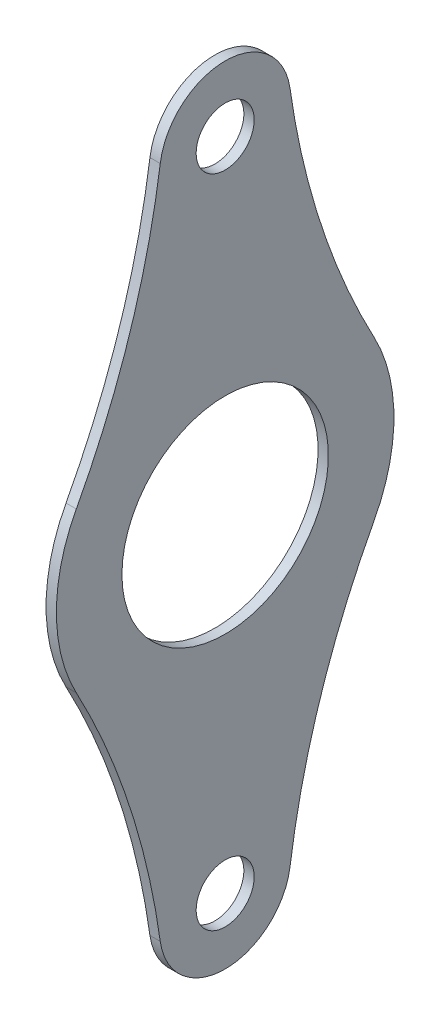
SolidWorks part; units mm, degrees
material "6061-T6 (SS)"
ref_plane "Front Plane" through (0, 0, 0) normal (0, 0, 1) x (1, 0, 0)
ref_plane "Top Plane" through (0, 0, 0) normal (0, 1, 0) x (1, 0, 0)
ref_plane "Right Plane" through (0, 0, 0) normal (1, 0, 0) x (0, 0, -1)
ref_plane "Plane1" through (56.0295, 0, 0) normal (-1, 0, 0) x (0, 0, 1)
sketch "Sketch1" plane through (56.0295, 0, 0) normal (-1, 0, 0) x (0, 0, 1)
  line L0 (-64.4299, 34.455) -> (-5.0306, 26.107) construction
  line L1 (-23.0873, 0) -> (0, 0) construction
  line L2 (0, 0) -> (0, 25.4) construction
  circle A2 centre (0, -25.4) radius 2.2479
  circle A3 centre (0, 25.4) radius 2.2479
  circle A4 centre (0, 0) radius 8.001
  circle A5 centre (0, 0) radius 6 construction
  arc A6 (-11.5352, 6.1686) -> (-11.5352, -6.1686) centre (0, 0) ccw
  arc A7 (5.0306, 26.107) -> (-5.0306, 26.107) centre (0, 25.4) ccw
  arc A8 (-5.0306, -26.107) -> (5.0306, -26.107) centre (0, -25.4) ccw
  arc A9 (-5.0306, 26.107) -> (-11.5352, 6.1686) centre (-64.4299, 34.455) cw
  arc A10 (5.0306, 26.107) -> (11.5352, 6.1686) centre (64.4299, 34.455) ccw
  arc A11 (5.0306, -26.107) -> (11.5352, -6.1686) centre (64.4299, -34.455) cw
  arc A12 (-5.0306, -26.107) -> (-11.5352, -6.1686) centre (-64.4299, -34.455) ccw
  arc A13 (11.5352, -6.1686) -> (11.5352, 6.1686) centre (0, 0) ccw
  circle A14 centre (0, 25.4) radius 2.2479 construction
  circle A15 centre (0, -25.4) radius 2.2479 construction
  dimension "D1" = 16.002
  dimension "D2" = 12
  dimension "D4" = 10.16
  dimension "D3" = 5.08
  dimension "D5" = 8
extrude "Boss-Extrude1" add sketch "Sketch1" along normal blind 0.8
equation "\"D1@Sketch1\"=.63in"
equation "\"D2@Sketch1\"=12mm"
equation "\"D1@Boss-Extrude2\"=4mm"
